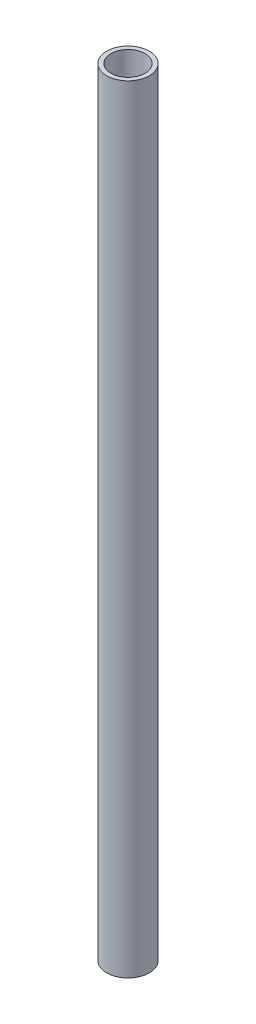
SolidWorks part; units mm, degrees
ref_plane "Front" through (0, 0, 0) normal (0, 0, 1) x (1, 0, 0)
ref_plane "Top" through (0, 0, 0) normal (0, 1, 0) x (1, 0, 0)
ref_plane "Right" through (0, 0, 0) normal (1, 0, 0) x (0, 0, -1)
sketch "Sketch1" plane through (0, 0, 0) normal (0, 1, 0) x (1, 0, 0)
  circle A0 centre (0, 0) radius 15.875
  circle A1 centre (0, 0) radius 12.7
  dimension "D1" = 31.75
  dimension "D2" = 25.4
extrude "Boss-Extrude1" add sketch "Sketch1" along normal mid plane 577.85
